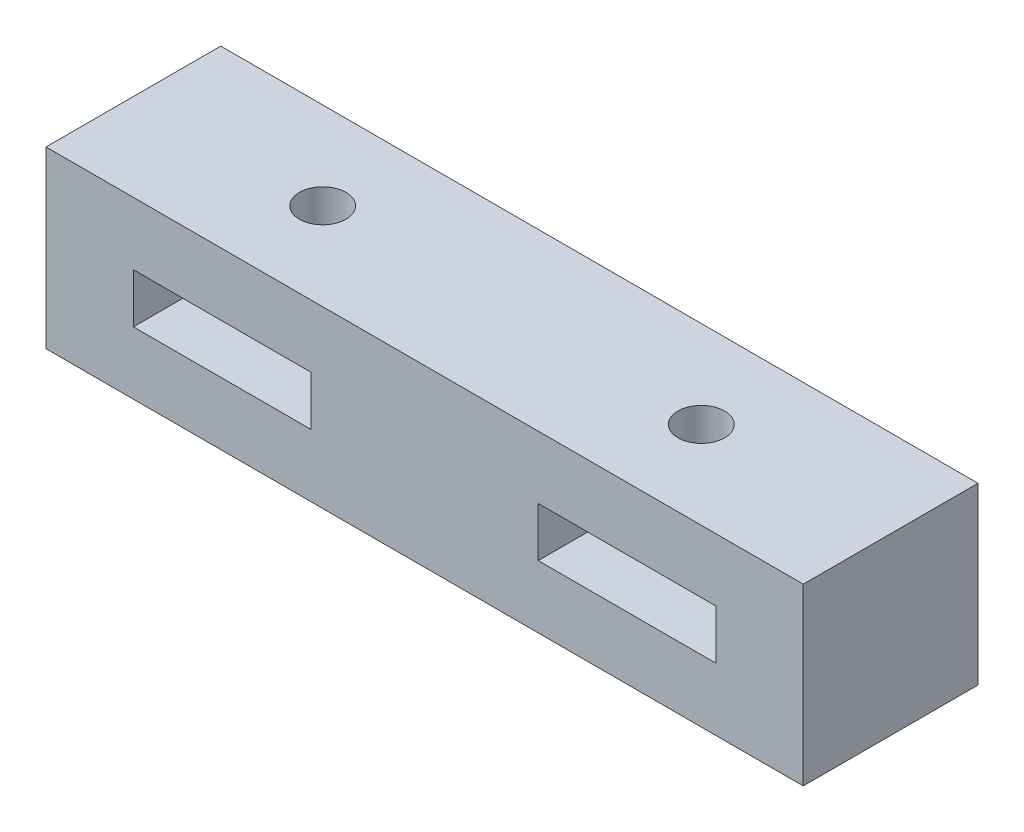
SolidWorks part; units mm, degrees
ref_plane "Alzado" through (0, 0, 0) normal (0, 0, 1) x (1, 0, 0)
ref_plane "Planta" through (0, 0, 0) normal (0, 1, 0) x (1, 0, 0)
ref_plane "Vista lateral" through (0, 0, 0) normal (1, 0, 0) x (0, 0, -1)
sketch "Croquis1" plane through (0, 0, 0) normal (0, 0, 1) x (1, 0, 0)
  line L0 (0, 0) -> (-26, 0) construction
  line L1 (-26, -6) -> (26, -6)
  line L2 (-26, -6) -> (-26, 6)
  line L3 (-26, 6) -> (26, 6)
  line L4 (26, -6) -> (26, 6)
  line L5 (-26, -6) -> (26, 6) construction
  line L6 (-26, 6) -> (26, -6) construction
  line L7 (0, 6) -> (0, -6) construction
  line L8 (20, 1.7) -> (7.8, 1.7)
  line L9 (-20, -1.7) -> (-7.8, -1.7)
  line L10 (-20, -1.7) -> (-20, 1.7)
  line L11 (-20, 1.7) -> (-7.8, 1.7)
  line L12 (-7.8, -1.7) -> (-7.8, 1.7)
  line L13 (-20, -1.7) -> (-7.8, 1.7) construction
  line L14 (-20, 1.7) -> (-7.8, -1.7) construction
  line L15 (7.8, -1.7) -> (7.8, 1.7)
  line L16 (20, -1.7) -> (7.8, -1.7)
  line L17 (20, -1.7) -> (20, 1.7)
  point P0 (0, 0)
  point P10 (-13.9, 0)
  dimension "D1" = 12
  dimension "D2" = 52
  dimension "D3" = 20
  dimension "D4" = 12.2
  dimension "D5" = 3.4
extrude "Saliente-Extruir1" add sketch "Croquis1" along normal mid plane 12
sketch "Croquis2" plane through (0, 0, -6) normal (0, 0, -1) x (-1, 0, 0)
  circle A0 centre (0, 0) radius 4.2687
  dimension "D1" = 8.5375
extrude "Cortar-Extruir1" cut sketch "Croquis2" against normal blind 11
sketch "Croquis3" plane through (0, 6, 0) normal (0, 1, 0) x (1, 0, 0)
  line L0 (-13, 6) -> (-13, -6) construction
  line L1 (26, 6) -> (-26, 6) construction
  line L2 (26, -6) -> (-26, -6) construction
  line L3 (0, 6) -> (0, -6) construction
  circle A0 centre (-13, 0) radius 1.6
  circle A1 centre (13, 0) radius 1.6
  dimension "D2" = 3.2
  dimension "D1" = 13
extrude "Cortar-Extruir2" cut sketch "Croquis3" against normal blind 30
